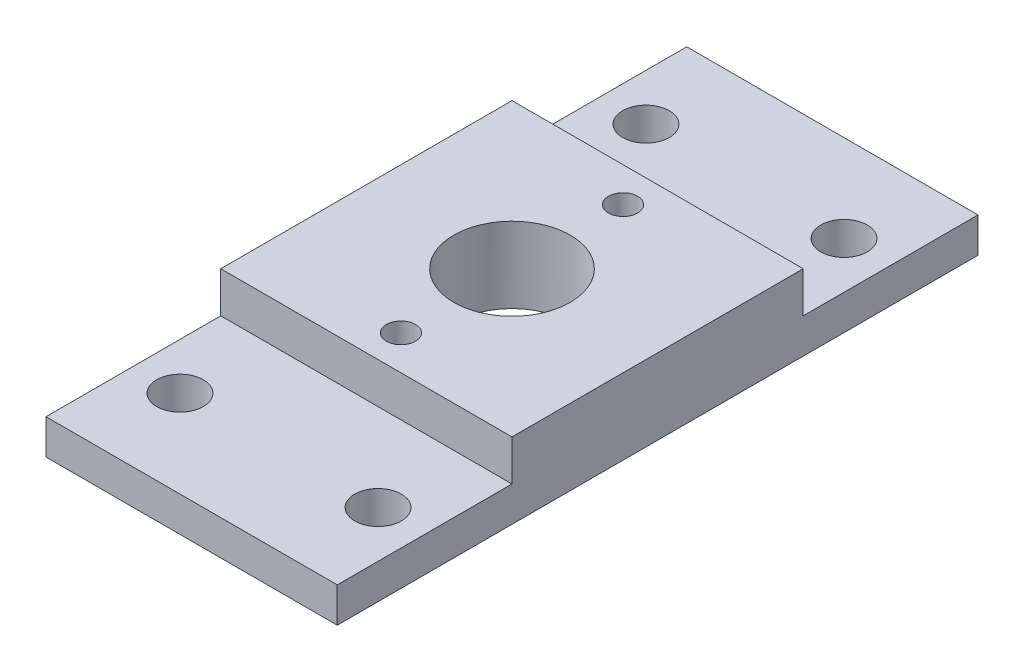
SolidWorks part; units mm, degrees
ref_plane "Front Plane" through (0, 0, 0) normal (0, 0, 1) x (1, 0, 0)
ref_plane "Top Plane" through (0, 0, 0) normal (0, 1, 0) x (1, 0, 0)
ref_plane "Right Plane" through (0, 0, 0) normal (1, 0, 0) x (0, 0, -1)
sketch "Sketch2" plane through (0, 0, 0) normal (1, 0, 0) x (0, 0, -1)
  line L0 (0, 0) -> (27.5, 0)
  line L1 (27.5, 0) -> (27.5, 3)
  line L2 (27.5, 3) -> (12.5, 3)
  line L3 (12.5, 3) -> (12.5, 6.5)
  line L4 (12.5, 6.5) -> (-12.5, 6.5)
  line L5 (-12.5, 6.5) -> (-12.5, 3)
  line L6 (-12.5, 3) -> (-27.5, 3)
  line L7 (-27.5, 3) -> (-27.5, 0)
  line L8 (-27.5, 0) -> (0, 0)
  dimension "D1" = 25
  dimension "D2" = 15
  dimension "D3" = 15
  dimension "D4" = 3
  dimension "D5" = 3.5
extrude "Boss-Extrude1" add sketch "Sketch2" along normal blind 12.5 and the other way blind 12.5
sketch "Sketch4" plane through (0, 3, 0) normal (0, 1, 0) x (1, 0, 0)
  line L0 (0, 27.5) -> (0, 12.5) construction
  line L1 (-12.5, 27.5) -> (12.5, 27.5) construction
  line L2 (-12.5, 12.5) -> (12.5, 12.5) construction
  line L3 (-12.5, 0) -> (12.5, 0) construction
  line L4 (-12.5, 12.5) -> (-12.5, -12.5) construction
  line L5 (12.5, 12.5) -> (12.5, -12.5) construction
  line L6 (-12.5, 27.5) -> (-12.5, 12.5) construction
  circle A0 centre (-8.5, 20) radius 2
  circle A1 centre (8.5, 20) radius 2
  circle A2 centre (8.5, -20) radius 2
  circle A3 centre (-8.5, -20) radius 2
  dimension "D1" = 4
  dimension "D3" = 17
  dimension "D2" = 4
  dimension "D4" = 40
extrude "Cut-Extrude2" cut sketch "Sketch4" against normal through all
sketch "Sketch7" plane through (0, 6.5, 0) normal (0, 1, 0) x (1, 0, 0)
  circle A0 centre (0, 0) radius 5
extrude "Cut-Extrude3" cut sketch "Sketch7" against normal up to next
hole_wizard "Tap Drill for M3x0.5 Tap2" positions "Sketch8" profile "Sketch9" hole size "M3x0.5" standard "ANSI Metric" end condition up to next
sketch "Sketch8" plane through (0, 6.5, 0) normal (0, 1, 0) x (1, 0, 0)
  point P0 (0, 9.53)
  point P2 (0, -9.53)
  dimension "D1" = 9.53
  dimension "D2" = 9.53
sketch "Sketch9" plane through (0, 6.5, -9.53) normal (1, 0, 0) x (0, 0, 1)
  line L0 (0, 0) -> (0, 6.5)
  line L1 (0, 6.5) -> (1.25, 6.5)
  line L2 (1.25, 6.5) -> (1.25, 0)
  line L5 (1.25, 0) -> (0, 0)
  line L11 (0, -6.35) -> (0, 107.95) construction
  dimension "Thru Hole Dia." = 2.5
  dimension "Thru Hole Depth" = 6.5
